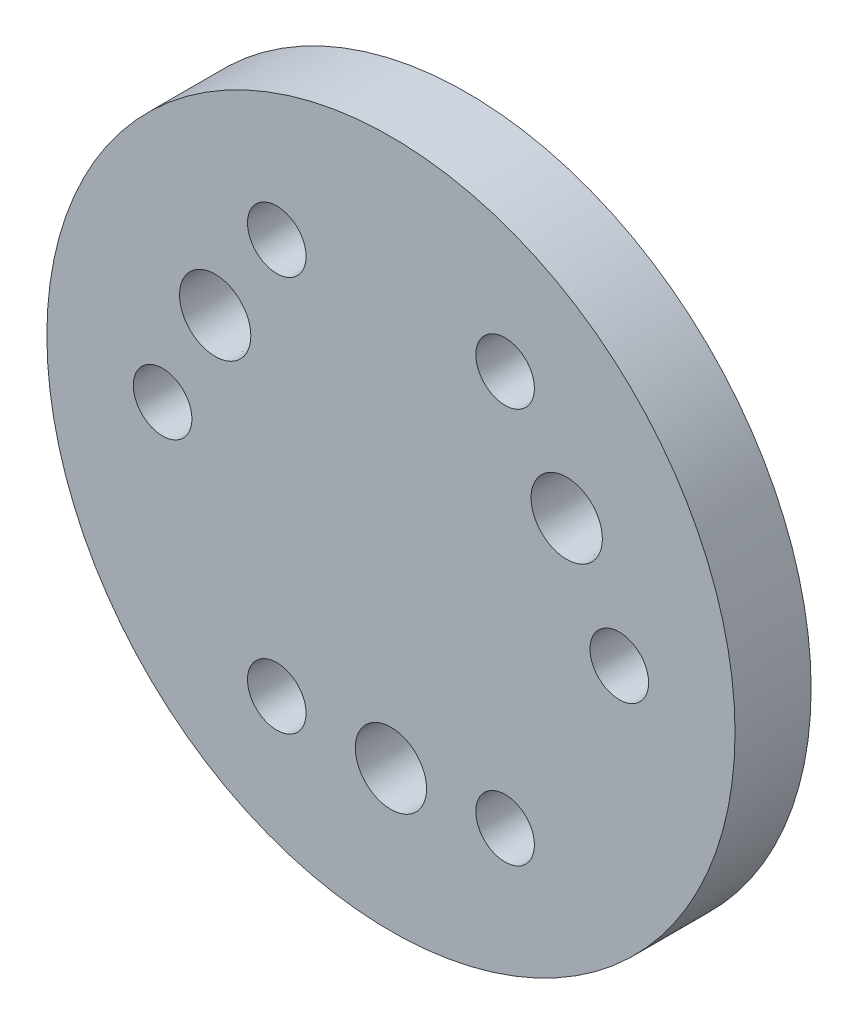
SolidWorks part; units mm, degrees
other "Markup1"
sketch "Sketch6" plane through (31.1257, -31.1257, 6.6) normal (0.5824, -0.4463, 0.6794) x (0.0162, 0.842, 0.5392)
ref_plane "Front Plane" through (0, 0, 0) normal (1, 0, 0) x (0, 1, 0)
ref_plane "Top Plane" through (0, 0, 0) normal (0, 0, 1) x (0, 1, 0)
ref_plane "Right Plane" through (0, 0, 0) normal (0, 1, 0) x (-1, 0, 0)
sketch "Sketch1" plane through (0, 0, 0) normal (0, 0, 1) x (0, 1, 0)
  circle A0 centre (0, 0) radius 27.125
  dimension "D1" = 54.25
extrude "Boss-Extrude1" add sketch "Sketch1" along normal blind 6 contours A0 region at (0, 0, 0)
sketch "Sketch2" plane through (0, 0, 6) normal (0, 0, -1) x (1, 0, 0)
  circle A0 centre (0, 0) radius 16 construction
  circle A1 centre (0, 16) radius 2.6
  circle A2 centre (13.8564, -8) radius 2.6
  circle A3 centre (-13.8564, -8) radius 2.6
  circle A4 centre (0, 0) radius 18 construction
  circle A5 centre (-9, -15.5885) radius 2.1
  circle A11 centre (-18, 0) radius 2.1
  circle A12 centre (-9, 15.5885) radius 2.1
  circle A13 centre (9, 15.5885) radius 2.1
  circle A14 centre (18, 0) radius 2.1
  circle A15 centre (9, -15.5885) radius 2.1
  dimension "D1" = 32
  dimension "D2" = 5.2
  dimension "D5" = 4.2
  dimension "D4" = 36
  dimension "D3" = 3
  dimension "D6" = 6
extrude "Cut-Extrude1" cut sketch "Sketch2" against normal through all draft 2 from surface draft outward yes starting at face at (27.125, 0, 0)
equation "\"SunTeeth\"= 12"
equation "\"PlanetTeeth\" = 20"
equation "\"Module\" = 1"
equation "\"OrbitDiameter\"= \"SunTeeth\" * \"Module\" + \"PlanetTeeth\" * \"Module\""
equation "\"RingDiameter\"= ( \"SunTeeth\" + 2 * \"PlanetTeeth\" ) * \"Module\""
equation "\"BearingBore\" = 4"
equation "\"D1@Sketch2\"=\"OrbitDiameter\""
equation "\"D2@Sketch2\"=5.2"
equation "\"PressureAngle\" = 20deg"
equation "\"GearWidth\"=10"
equation "\"BearingDiameter\" = 13"
equation "\"ShaftDiameter\"= 6.5"
equation "\"D1@Sketch1\"=( \"SunTeeth\" + 2 * \"PlanetTeeth\" ) * \"Module\"+ 2.25*\"Module\""
